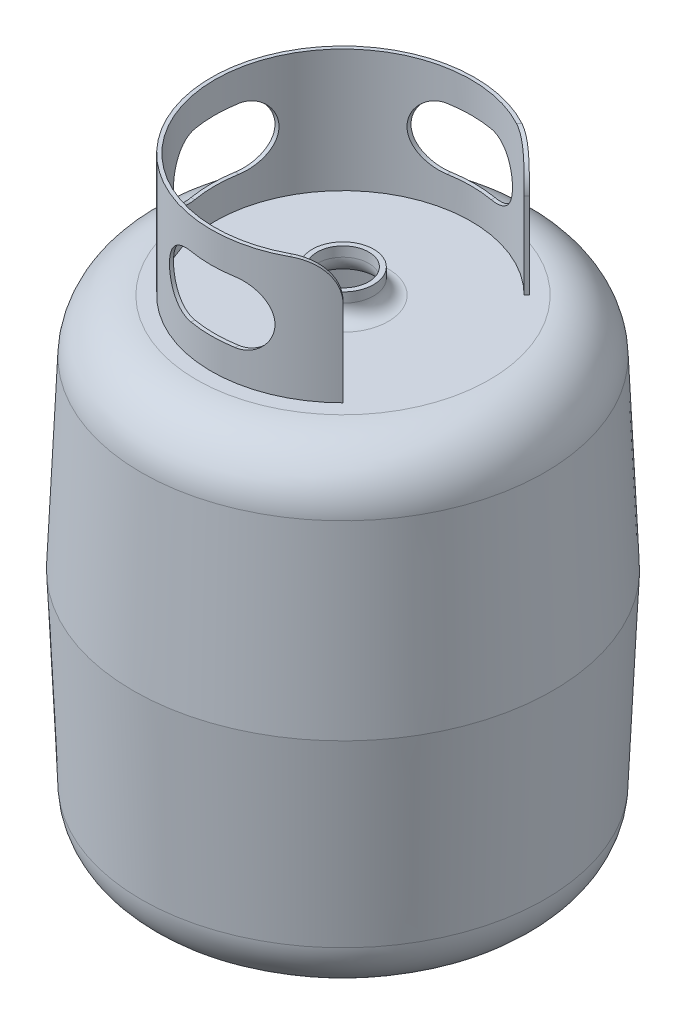
SolidWorks part; units mm, degrees
material "1060 Alloy"
ref_plane "Front Plane" through (0, 0, 0) normal (0, 0, 1) x (1, 0, 0)
ref_plane "Top Plane" through (0, 0, 0) normal (0, 1, 0) x (1, 0, 0)
ref_plane "Right Plane" through (0, 0, 0) normal (1, 0, 0) x (0, 0, -1)
sketch "Sketch1" plane through (0, 0, 0) normal (0, 0, 1) x (1, 0, 0)
  line L0 (0, 0) -> (0, -407.5) construction
  line L1 (0, 0) -> (-25, 0)
  line L2 (-25, 0) -> (-25, -8)
  line L3 (-37, -20) -> (-119.4219, -20)
  line L4 (-164.379, -63.0371) -> (-170.9593, -213.75)
  line L5 (-170.9593, -213.75) -> (-164.379, -364.4629)
  line L6 (-119.4219, -407.5) -> (0, -407.5)
  line L7 (0, -4) -> (-21, -4)
  line L8 (-21, -4) -> (-21, -8)
  line L9 (-37, -24) -> (-119.4219, -24)
  line L10 (-160.3828, -63.2116) -> (-166.9555, -213.75)
  line L11 (-166.9555, -213.75) -> (-160.3828, -364.2884)
  line L12 (-119.4219, -403.5) -> (0, -403.5)
  line L13 (0, 0) -> (0, -4)
  line L14 (0, -403.5) -> (0, -407.5)
  arc A0 (-25, -8) -> (-37, -20) centre (-37, -8) cw
  arc A1 (-164.379, -364.4629) -> (-119.4219, -407.5) centre (-119.4219, -362.5) ccw
  arc A2 (-119.4219, -20) -> (-164.379, -63.0371) centre (-119.4219, -65) ccw
  arc A3 (-21, -8) -> (-37, -24) centre (-37, -8) cw
  arc A4 (-119.4219, -24) -> (-160.3828, -63.2116) centre (-119.4219, -65) ccw
  arc A5 (-160.3828, -364.2884) -> (-119.4219, -403.5) centre (-119.4219, -362.5) ccw
  point P10 (-25, -20)
  point P13 (-162.5, -407.5)
  point P16 (-162.5, -20)
  dimension "D8" = 12
  dimension "D9" = 45
  dimension "D1" = 407.5
  dimension "D2" = 20
  dimension "D3" = 25
  dimension "D4" = 325
  dimension "D5" = 162.5
  dimension "D6" = 92.5
  dimension "D7" = 92.5
  dimension "D10" = 4
revolve "Revolve1" add sketch "Sketch1" angle 360 about L0
sketch "Sketch2" plane through (0, 0, 0) normal (0, 1, 0) x (1, 0, 0)
  circle A0 centre (0, 0) radius 21
  circle A1 centre (0, 0) radius 25 construction
  dimension "D1" = 4
extrude "Cut-Extrude1" cut sketch "Sketch2" against normal blind 40
sketch "Sketch3" plane through (0, -20, 0) normal (0, 1, 0) x (1, 0, 0)
  line L0 (0, 0) -> (75.9587, 75.9587)
  line L1 (0, 0) -> (75.9587, -75.9587)
  circle A0 centre (0, 0) radius 107.4219
  circle A1 centre (0, 0) radius 119.4219 construction
  circle A2 centre (0, 0) radius 104.4219
  dimension "D1" = 12
  dimension "D2" = 3
  dimension "D3" = 45
  dimension "D4" = 45
extrude "Boss-Extrude1" add sketch "Sketch3" along normal blind 100 contours A2 L0 A0 L1 region at (-107.2465, -20, 0)
fillet "Fillet1" radius 30 2 edges at (74.8981, 80, -74.8981) (74.8981, 80, 74.8981)
sketch "Sketch4" plane through (0, 0, 0) normal (0, 0, 1) x (1, 0, 0)
  line L0 (-18, 30) -> (18, 30) construction
  line L1 (-18, 55) -> (18, 55)
  line L2 (-18, 5) -> (18, 5)
  line L3 (49.5114, 80) -> (-104.4219, 80) construction
  arc A0 (-18, 55) -> (-18, 5) centre (-18, 30) ccw
  arc A1 (18, 5) -> (18, 55) centre (18, 30) ccw
  point P2 (0, 30)
  point P10 (-43, 30)
  point P11 (43, 30)
  dimension "D1" = 18
  dimension "D2" = 50
  dimension "D3" = 50
  dimension "D4" = 86
extrude "Cut-Extrude2" cut sketch "Sketch4" against normal through all both and the other way through all
pattern_circular "CirPattern1" count 2 every 90 about axis through (0, 80, 0) along (0, 1, 0) of "Cut-Extrude2"
